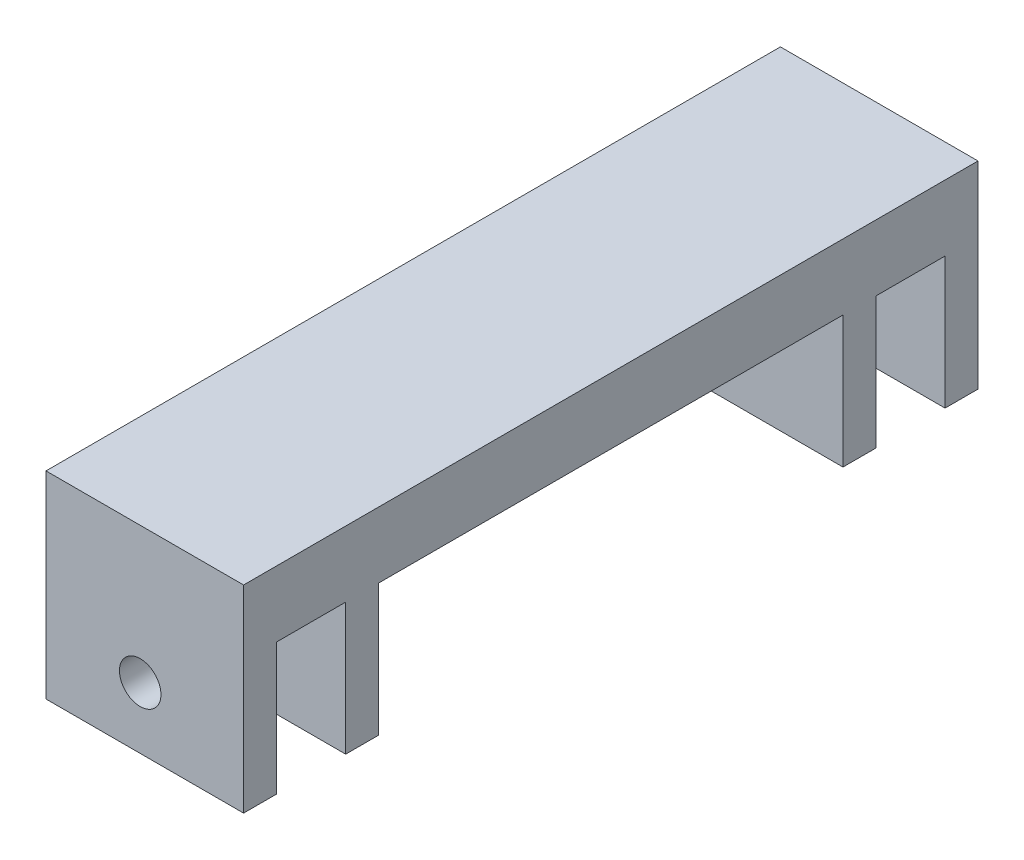
SolidWorks part; units mm, degrees
ref_plane "Plan de face" through (0, 0, 0) normal (0, 0, 1) x (1, 0, 0)
ref_plane "Plan de dessus" through (0, 0, 0) normal (0, 1, 0) x (1, 0, 0)
ref_plane "Plan de droite" through (0, 0, 0) normal (1, 0, 0) x (0, 0, -1)
sketch "Esquisse1" plane through (0, 0, 0) normal (0, 0, 1) x (1, 0, 0)
  line L1 (0, 0) -> (30, 0)
  line L2 (0, 0) -> (0, 10)
  line L3 (0, 10) -> (30, 10)
  line L4 (30, 0) -> (30, 10)
  dimension "D1" = 30
  dimension "D2" = 10
extrude "Boss.-Extru.1" add sketch "Esquisse1" along normal blind 111.5
sketch "Esquisse2" plane through (0, 0, 0) normal (0, -1, 0) x (1, 0, 0)
  line L0 (30, 111.5) -> (30, 0) construction
  line L1 (0, 0) -> (30, 0)
  line L2 (0, 0) -> (0, 5)
  line L3 (0, 5) -> (30, 5)
  line L4 (30, 0) -> (30, 5)
  line L5 (0, 111.5) -> (0, 0) construction
  line L6 (30, 15.5) -> (0, 15.5)
  line L7 (30, 15.5) -> (30, 20.5)
  line L8 (30, 20.5) -> (0, 20.5)
  line L9 (0, 15.5) -> (0, 20.5)
  line L11 (0, 111.5) -> (30, 111.5)
  line L12 (0, 111.5) -> (0, 106.5)
  line L13 (0, 106.5) -> (30, 106.5)
  line L14 (30, 111.5) -> (30, 106.5)
  line L15 (30, 96) -> (0, 96)
  line L16 (30, 96) -> (30, 91)
  line L17 (30, 91) -> (0, 91)
  line L18 (0, 96) -> (0, 91)
  dimension "D1" = 5
  dimension "D2" = 5
  dimension "D3" = 5
  dimension "D4" = 5
  dimension "D5" = 10.5
  dimension "D6" = 10.5
extrude "Boss.-Extru.2" add sketch "Esquisse2" along normal blind 20
sketch "Esquisse3" plane through (0, 0, 111.5) normal (0, 0, 1) x (1, 0, 0)
  line L0 (30, -20) -> (0, -20) construction
  line L1 (30, -20) -> (30, 10) construction
  circle A0 centre (14.3021, -10.6869) radius 3.15
  dimension "D1" = 6.3
  dimension "D2" = 9.3131
  dimension "D3" = 15.6979
extrude "Enlèv. mat.-Extru.2" cut sketch "Esquisse3" against normal through all
